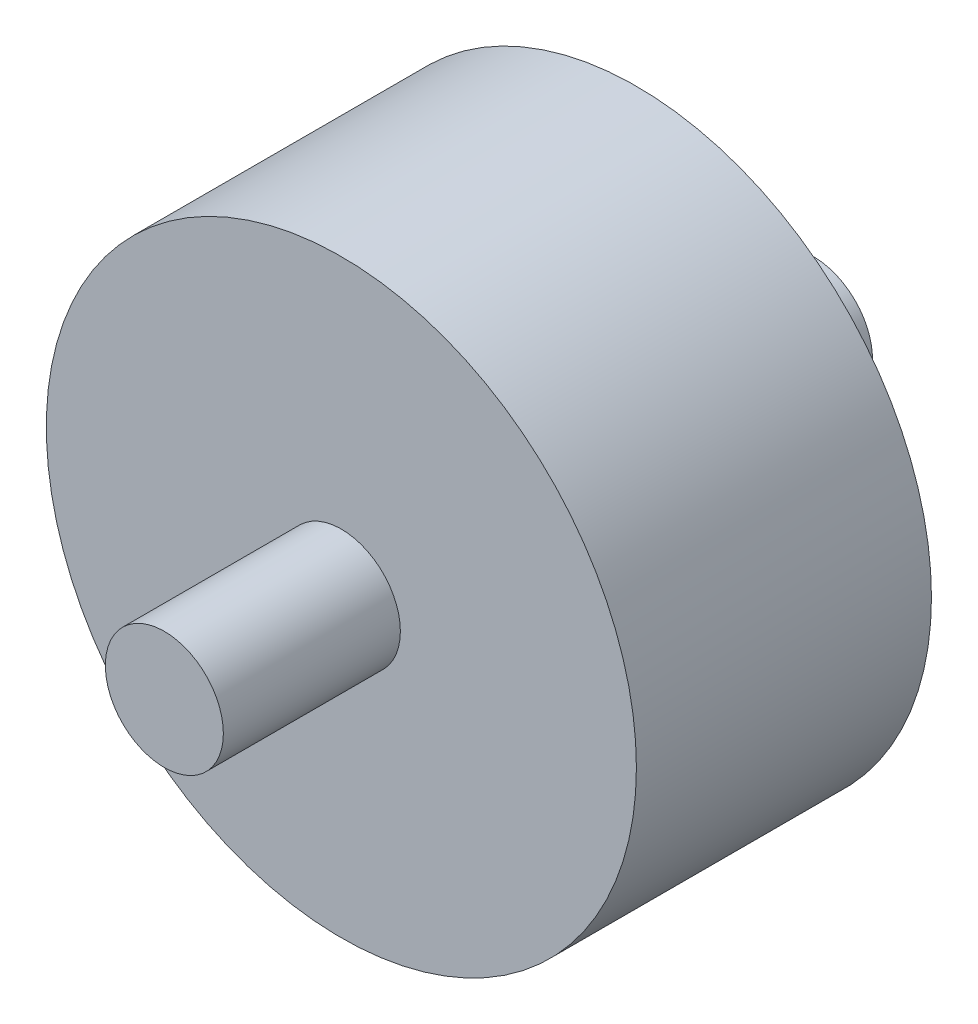
SolidWorks part; units mm, degrees
ref_plane "Front Plane" through (0, 0, 0) normal (0, 0, 1) x (1, 0, 0)
ref_plane "Top Plane" through (0, 0, 0) normal (0, 1, 0) x (1, 0, 0)
ref_plane "Right Plane" through (0, 0, 0) normal (1, 0, 0) x (0, 0, -1)
sketch "Sketch1" plane through (0, 0, 0) normal (0, 0, 1) x (1, 0, 0)
  circle A0 centre (0, 0) radius 50
  dimension "D1" = 100
extrude "Boss-Extrude1" add sketch "Sketch1" along normal mid plane 50
sketch "Sketch2" plane through (0, 0, -25) normal (0, 0, -1) x (-1, 0, 0)
  circle A0 centre (0, 0) radius 10
  dimension "D1" = 20
extrude "Boss-Extrude2" add sketch "Sketch2" along normal blind 30
sketch "Sketch3" plane through (0, 0, 25) normal (0, 0, 1) x (1, 0, 0)
  circle A0 centre (0, 0) radius 10
  dimension "D1" = 20
extrude "Boss-Extrude3" add sketch "Sketch3" along normal blind 30
